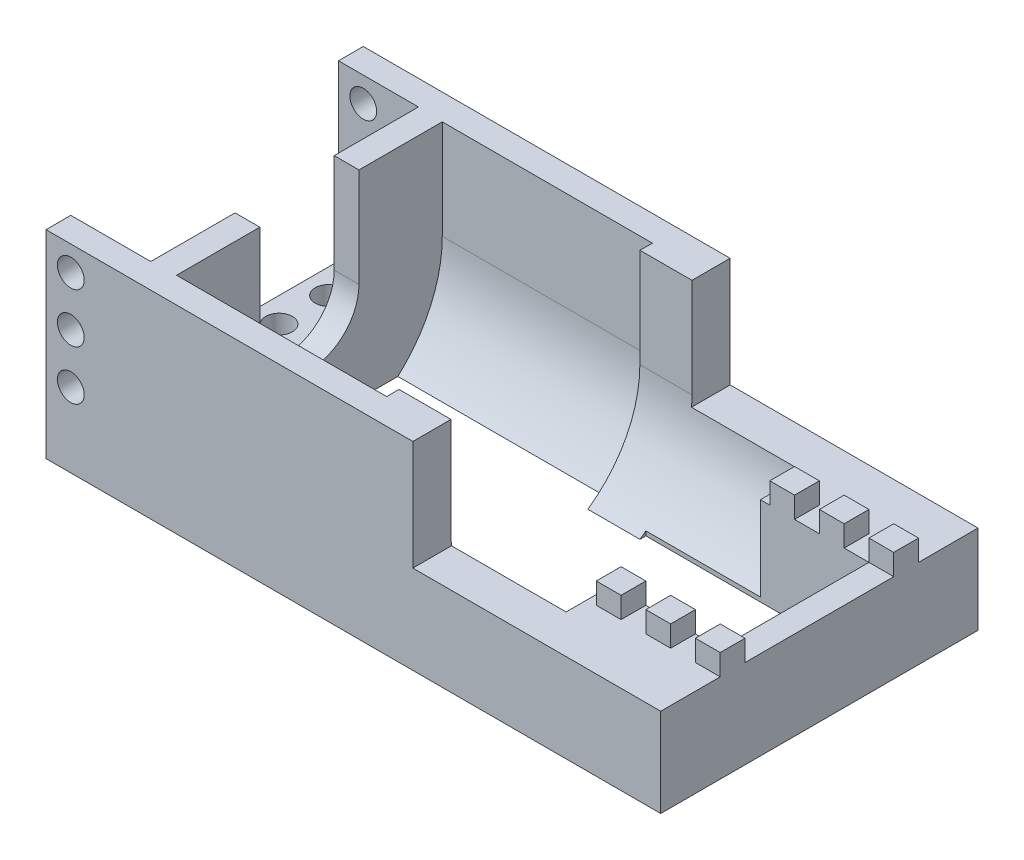
SolidWorks part; units mm, degrees
ref_plane "Front Plane" through (0, 0, 0) normal (0, 0, 1) x (1, 0, 0)
ref_plane "Top Plane" through (0, 0, 0) normal (0, 1, 0) x (1, 0, 0)
ref_plane "Right Plane" through (0, 0, 0) normal (1, 0, 0) x (0, 0, -1)
sketch "Sketch1" plane through (0, 0, 0) normal (0, 0, 1) x (1, 0, 0)
  line L1 (-76.2, -50.8) -> (81.28, -50.8)
  line L2 (-76.2, -50.8) -> (-76.2, 0)
  line L3 (-76.2, 0) -> (81.28, 0)
  line L4 (81.28, -50.8) -> (81.28, 0)
  line L5 (-76.2, -50.8) -> (81.28, 0) construction
  line L6 (-76.2, 0) -> (81.28, -50.8) construction
  point P0 (0, 0)
  dimension "D1" = 157.48
  dimension "D2" = 50.8
  dimension "D3" = 76.2
extrude "Boss-Extrude1" add sketch "Sketch1" along normal mid plane 81.28
sketch "Sketch2" plane through (0, 0, 0) normal (0, 0, 1) x (1, 0, 0)
  line L1 (-49.3609, 8.636) -> (-49.3609, -12.7)
  line L3 (81.28, 0) -> (-76.2, 0) construction
  line L4 (4.4871, 8.636) -> (4.4373, 5.4614)
  line L5 (3.9535, -25.4) -> (4.4871, 8.636) construction
  line L6 (-76.2, -25.4) -> (19.6294, -25.4)
  line L7 (19.6294, -25.4) -> (72.5335, -25.4)
  line L8 (-607.3619, -25.4) -> (19.6294, -25.4) construction
  line L9 (-49.3609, 8.636) -> (4.4871, 8.636)
  line L11 (4.4373, 5.4614) -> (47.1335, 5.4614)
  line L12 (47.1335, 5.4614) -> (47.1335, -15.494)
  line L13 (47.1335, -15.494) -> (72.5335, -15.494)
  line L14 (-49.3609, -12.7) -> (-76.2, -12.7)
  line L15 (-76.2, -12.7) -> (-76.2, -25.4)
  line L16 (81.28, 0) -> (-76.2, 0) construction
  line L17 (-76.2, 0) -> (-76.2, -50.8) construction
  line L20 (72.5335, -15.494) -> (72.5335, -25.4)
  line L21 (-76.2, 0) -> (-76.2, -50.8) construction
  point P8 (0, 0)
  point P23 (3.9535, -25.4)
  dimension "D1" = 25.4
  dimension "D2" = 53.848
  dimension "D3" = 34.036
  dimension "D4" = 68.58
  dimension "D5" = 9.906
  dimension "D6" = 3.175
  dimension "D7" = 26.8391
  dimension "D8" = 25.4
  dimension "D9" = 12.7
revolve "Cut-Revolve1" cut sketch "Sketch2" angle 360 about L8
sketch "Sketch37" plane through (81.28, 0, 0) normal (1, 0, 0) x (0, 0, -1)
  line L0 (40.64, -50.8) -> (40.64, 0) construction
  line L1 (-40.64, 0) -> (40.64, 0)
  line L2 (-40.64, 0) -> (-40.64, -25.4)
  line L3 (-40.64, -25.4) -> (40.64, -25.4)
  line L4 (40.64, 0) -> (40.64, -25.4)
  point P7 (0, -25.4)
  point P11 (0, 0)
  dimension "D1" = 25.4
extrude "Cut-Extrude32" cut sketch "Sketch37" against normal through all
sketch "Sketch39" plane through (0, -25.4, 0) normal (0, 1, 0) x (1, 0, 0)
  line L20 (-49.3609, -12.7) -> (-76.2, -12.7)
  line L21 (-49.3609, -12.7) -> (-76.2, -12.7)
  line L22 (-76.2, 40.64) -> (-76.2, 12.7)
  line L23 (-76.2, 40.64) -> (-76.2, 12.7)
  line L24 (-76.2, 12.7) -> (-49.3609, 12.7)
  line L25 (-76.2, -12.7) -> (-76.2, -40.64)
  line L26 (-76.2, -40.64) -> (81.28, -40.64)
  line L27 (81.28, -40.64) -> (81.28, 40.64)
  line L28 (81.28, 40.64) -> (-76.2, 40.64)
  line L29 (-76.2, 12.7) -> (-49.3609, 12.7)
  line L30 (-49.3609, 12.7) -> (-49.3609, 34.036)
  line L31 (-49.3609, 12.7) -> (-49.3609, 34.036)
  line L32 (-49.3609, 34.036) -> (4.4871, 34.036)
  line L33 (-49.3609, 34.036) -> (4.4871, 34.036)
  line L34 (4.4871, 34.036) -> (4.4373, 30.8614)
  line L35 (4.4871, 34.036) -> (4.4373, 30.8614)
  line L36 (4.4373, 30.8614) -> (47.1335, 30.8614)
  line L37 (4.4373, 30.8614) -> (47.1335, 30.8614)
  line L38 (47.1335, 30.8614) -> (47.1335, 9.906)
  line L39 (47.1335, 30.8614) -> (47.1335, 9.906)
  line L40 (47.1335, 9.906) -> (72.5335, 9.906)
  line L41 (47.1335, 9.906) -> (72.5335, 9.906)
  line L42 (72.5335, 9.906) -> (72.5335, -9.906)
  line L43 (72.5335, 9.906) -> (72.5335, -9.906)
  line L44 (72.5335, -9.906) -> (47.1335, -9.906)
  line L45 (72.5335, -9.906) -> (47.1335, -9.906)
  line L46 (47.1335, -9.906) -> (47.1335, -30.8614)
  line L47 (47.1335, -9.906) -> (47.1335, -30.8614)
  line L48 (47.1335, -30.8614) -> (4.4373, -30.8614)
  line L49 (-76.2, -12.7) -> (-76.2, -40.64)
  line L50 (-76.2, -40.64) -> (81.28, -40.64)
  line L51 (81.28, -40.64) -> (81.28, 40.64)
  line L52 (81.28, 40.64) -> (-76.2, 40.64)
  line L53 (47.1335, -30.8614) -> (4.4373, -30.8614)
  line L54 (4.4373, -30.8614) -> (4.4871, -34.036)
  line L55 (4.4373, -30.8614) -> (4.4871, -34.036)
  line L56 (4.4871, -34.036) -> (-49.3609, -34.036)
  line L57 (4.4871, -34.036) -> (-49.3609, -34.036)
  line L58 (-49.3609, -34.036) -> (-49.3609, -12.7)
  line L59 (-49.3609, -34.036) -> (-49.3609, -12.7)
  dimension "D1" = 0
extrude "Boss-Extrude5" add sketch "Sketch39" along normal blind 25.4
ref_axis "Axis1" through (72.5335, -25.4, 0) along (-1, 0, 0)
ref_plane "Plane_Mid" through (0, -25.4, 0) normal (0, 1, 0) x (1, 0, 0)
ref_plane "Plane3" through (0, -28.0987, 0) normal (0, 1, 0) x (1, 0, 0)
sketch "Sketch45" plane through (0, 0, 0) normal (0, 0, 1) x (1, 0, 0)
  line L1 (27.94, -28.0987) -> (-27.94, -28.0988) construction
  line L2 (81.28, 0) -> (17.78, 0)
  line L4 (81.28, 0) -> (81.28, -28.0987)
  line L5 (81.28, -28.0987) -> (17.78, -28.0987)
  line L8 (17.78, 0) -> (17.78, -28.0987)
  dimension "D1" = 63.5
extrude "Cut-Extrude54" cut sketch "Sketch45" against normal through all both and the other way through all
ref_plane "Plane1" through (-74.7609, 0, 0) normal (1, 0, 0) x (0, 0, -1)
sketch "Sketch97" plane through (0, 0, 0) normal (0, 1, 0) x (1, 0, 0)
  line L0 (-76.2, -40.64) -> (17.78, -40.64) construction
  line L1 (-76.2, 40.64) -> (-55.7109, 40.64)
  line L2 (-76.2, 40.64) -> (-76.2, -40.64)
  line L3 (-76.2, -40.64) -> (-55.7109, -40.64)
  line L4 (-55.7109, 40.64) -> (-55.7109, -40.64)
  line L5 (-49.3609, 12.7) -> (-49.3609, 34.036) construction
  dimension "D1" = 6.35
extrude "Cut-Extrude72" cut sketch "Sketch97" against normal offset from surface (44.45 mm away) 6.35 up to face at (2.54, -50.8, 0)
sketch "Sketch98" plane through (0, -44.45, 0) normal (0, 1, 0) x (1, 0, 0)
  line L0 (-76.2, -40.64) -> (-76.2, 40.64) construction
  circle A0 centre (-69.85, 25.4) radius 3.429
  circle A4 centre (-69.85, 12.7) radius 3.429
  circle A5 centre (-69.85, 0) radius 3.429
  circle A6 centre (-57.15, 25.4) radius 3.429 [skipped]
  circle A7 centre (-57.15, 12.7) radius 3.429 [skipped]
  circle A8 centre (-57.15, 0) radius 3.429 [skipped]
  circle A9 centre (-69.85, -12.7) radius 3.429
  circle A11 centre (-69.85, -25.4) radius 3.429
  circle A13 centre (-57.15, -12.7) radius 3.429 [skipped]
  circle A14 centre (-57.15, -25.4) radius 3.429 [skipped]
  dimension "D1" = 6.858
  dimension "D2" = 76.2
  dimension "D3" = 6.35
  dimension "D4" = 25.4
  dimension "D5" = 2
  dimension "D6" = 5
extrude "Cut-Extrude73" cut sketch "Sketch98" against normal through all
ref_plane "Plane2" through (0, -25.4, 0) normal (0, 1, 0) x (1, 0, 0)
ref_point "Point1"
sketch "Sketch99" plane through (0, 0, 0) normal (0, 1, 0) x (1, 0, 0)
  line L8 (81.28, 40.64) -> (81.28, -40.64) construction
  line L9 (17.78, 19.05) -> (74.93, 19.05)
  line L10 (17.78, 19.05) -> (17.78, -19.05)
  line L11 (17.78, -19.05) -> (74.93, -19.05)
  line L12 (74.93, 19.05) -> (74.93, -19.05)
  line L15 (17.78, 40.64) -> (17.78, 30.8614) construction
  point P7 (74.93, 0)
  dimension "D1" = 6.35
  dimension "D2" = 38.1
extrude "Cut-Extrude74" cut sketch "Sketch99" against normal through all
sketch "Sketch101" plane through (0, -28.0988, 0) normal (0, 1, 0) x (1, 0, 0)
  line L0 (49.53, 25.4) -> (55.88, 25.4)
  line L1 (49.53, 25.4) -> (49.53, 19.05)
  line L2 (49.53, 19.05) -> (55.88, 19.05)
  line L3 (55.88, 25.4) -> (55.88, 19.05)
  line L4 (62.23, 25.4) -> (68.58, 25.4)
  line L5 (62.23, 25.4) -> (62.23, 19.05)
  line L6 (62.23, 19.05) -> (68.58, 19.05)
  line L7 (68.58, 25.4) -> (68.58, 19.05)
  line L8 (74.93, 25.4) -> (81.28, 25.4)
  line L9 (74.93, 25.4) -> (74.93, 19.05)
  line L10 (74.93, 19.05) -> (81.28, 19.05)
  line L11 (81.28, 25.4) -> (81.28, 19.05)
  line L13 (81.28, 0) -> (0, 0) construction
  line L14 (81.28, 40.64) -> (81.28, -40.64) construction
  line L15 (81.28, -25.4) -> (81.28, -19.05)
  line L16 (74.93, -19.05) -> (81.28, -19.05)
  line L17 (74.93, -25.4) -> (74.93, -19.05)
  line L18 (74.93, -25.4) -> (81.28, -25.4)
  line L19 (68.58, -25.4) -> (68.58, -19.05)
  line L20 (62.23, -19.05) -> (68.58, -19.05)
  line L21 (62.23, -25.4) -> (62.23, -19.05)
  line L22 (62.23, -25.4) -> (68.58, -25.4)
  line L23 (55.88, -25.4) -> (55.88, -19.05)
  line L24 (49.53, -19.05) -> (55.88, -19.05)
  line L25 (49.53, -25.4) -> (49.53, -19.05)
  line L26 (49.53, -25.4) -> (55.88, -25.4)
  point P30 (79.8658, 25.2405)
  point P31 (74.93, 22.225)
  dimension "D1" = 6.35
  dimension "D2" = 6.35
  dimension "D3" = 6.35
extrude "Boss-Extrude7" add sketch "Sketch101" along normal blind 5.3975
sketch "Sketch102" plane through (0, 0, 0) normal (0, 1, 0) x (1, 0, 0)
  line L0 (-76.2, -40.64) -> (-76.2, 40.64) construction
  line L1 (-55.7109, 40.64) -> (-76.2, 40.64)
  line L2 (-55.7109, 40.64) -> (-55.7109, 34.29)
  line L3 (-55.7109, 34.29) -> (-76.2, 34.29)
  line L4 (-76.2, 40.64) -> (-76.2, 34.29)
  line L5 (-55.7109, -40.64) -> (-76.2, -40.64)
  line L6 (-55.7109, -40.64) -> (-55.7109, -34.29)
  line L7 (-55.7109, -34.29) -> (-76.2, -34.29)
  line L8 (-76.2, -40.64) -> (-76.2, -34.29)
  dimension "D1" = 6.35
extrude "Boss-Extrude8" add sketch "Sketch102" against normal up to next
sketch "Sketch103" plane through (0, 0, 40.64) normal (0, 0, 1) x (1, 0, 0)
  line L0 (-76.2, 0) -> (-76.2, -50.8) construction
  line L1 (-76.2, 0) -> (17.78, 0) construction
  circle A0 centre (-69.85, -6.35) radius 3.429
  circle A1 centre (-69.85, -19.05) radius 3.429
  circle A2 centre (-69.85, -31.75) radius 3.429
  circle A4 centre (-69.85, -44.45) radius 3.429 [skipped]
  dimension "D1" = 6.858
  dimension "D2" = 6.35
  dimension "D3" = 6.35
  dimension "D4" = 4
extrude "Cut-Extrude75" cut sketch "Sketch103" against normal through all
